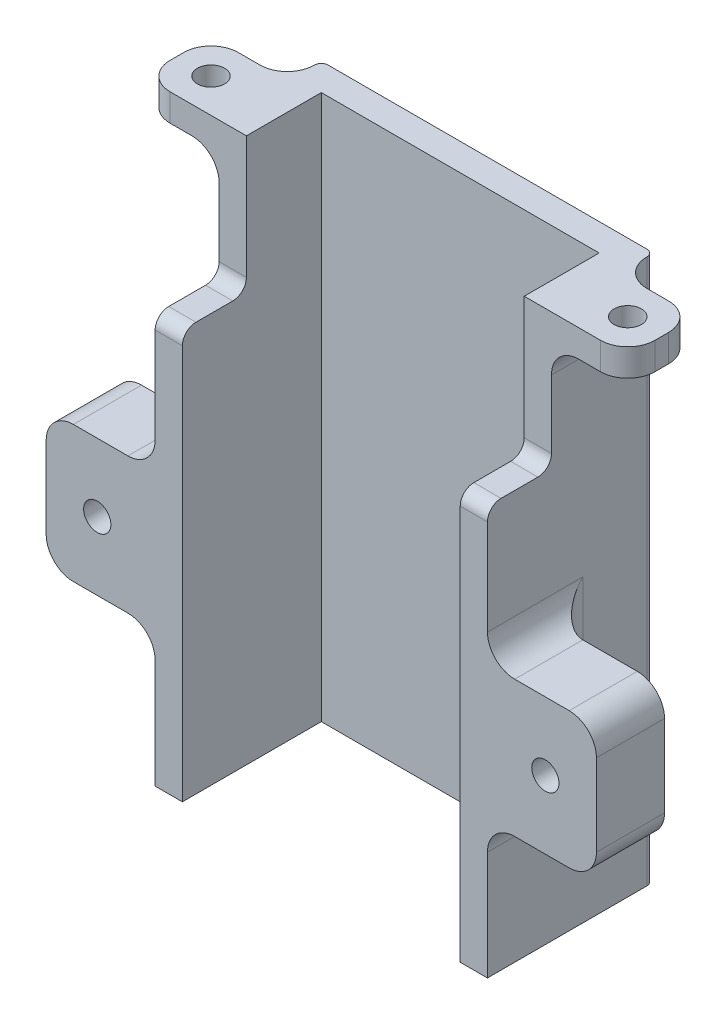
SolidWorks part; units mm, degrees
ref_plane "Front Plane" through (0, 0, 0) normal (0, 0, 1) x (1, 0, 0)
ref_plane "Top Plane" through (0, 0, 0) normal (0, 1, 0) x (1, 0, 0)
ref_plane "Right Plane" through (0, 0, 0) normal (1, 0, 0) x (0, 0, -1)
sketch "Sketch1" plane through (0, 0, 0) normal (0, 1, 0) x (1, 0, 0)
  line L1 (-25.908, 12.954) -> (25.908, 12.954)
  line L2 (-25.908, 12.954) -> (-25.908, -12.954)
  line L3 (-25.908, -12.954) -> (25.908, -12.954)
  line L4 (25.908, 12.954) -> (25.908, -12.954)
  line L5 (-25.908, 12.954) -> (25.908, -12.954) construction
  line L6 (-25.908, -12.954) -> (25.908, 12.954) construction
  line L7 (-30.988, -12.954) -> (30.988, -12.954)
  line L8 (-30.988, -12.954) -> (-30.988, 18.034)
  line L9 (-30.988, 18.034) -> (30.988, 18.034)
  line L10 (30.988, -12.954) -> (30.988, 18.034)
  point P0 (0, 0)
  dimension "D1" = 51.816
  dimension "D2" = 25.908
  dimension "D3" = 5.08
  dimension "D4" = 5.08
  dimension "D5" = 5.08
extrude "Boss-Extrude1" add sketch "Sketch1" along normal blind 101.6 contours L7 L10 L9 L8 L2 L1 L4 region at (-26.6009, 0, 0)
sketch "Sketch2" plane through (0, 0, 12.954) normal (0, 0, 1) x (1, 0, 0)
  line L0 (25.908, 101.6) -> (25.908, 0) construction
  line L1 (25.908, 25.4) -> (51.308, 25.4)
  line L2 (25.908, 25.4) -> (25.908, 50.8)
  line L3 (25.908, 50.8) -> (51.308, 50.8)
  line L4 (51.308, 25.4) -> (51.308, 50.8)
  line L5 (25.908, 101.6) -> (30.988, 101.6) construction
  line L6 (0, 0) -> (0, 80.1412) construction
  line L7 (-51.308, 25.4) -> (-51.308, 50.8)
  line L8 (-25.908, 50.8) -> (-51.308, 50.8)
  line L9 (-25.908, 25.4) -> (-25.908, 50.8)
  line L10 (-25.908, 25.4) -> (-51.308, 25.4)
  dimension "D1" = 25.4
  dimension "D2" = 25.4
  dimension "D3" = 50.8
extrude "Boss-Extrude2" add sketch "Sketch2" against normal blind 12.7
sketch "Sketch3" plane through (0, 0, 0.254) normal (0, 0, -1) x (-1, 0, 0)
  line L0 (-51.308, 50.8) -> (-30.988, 50.8) construction
  line L1 (-51.308, 25.4) -> (-51.308, 50.8) construction
  line L2 (0, 73.8565) -> (0, 0) construction
  circle A0 centre (-41.783, 38.1) radius 2.54
  circle A1 centre (41.783, 38.1) radius 2.54
  dimension "D1" = 5.08
  dimension "D2" = 12.7
  dimension "D3" = 9.525
extrude "Cut-Extrude1" cut sketch "Sketch3" against normal through all
sketch "Sketch4" plane through (0, 0, 0.254) normal (0, 0, -1) x (-1, 0, 0)
  circle A0 centre (-41.783, 38.1) radius 6.35
  circle A1 centre (41.783, 38.1) radius 6.35
  dimension "D1" = 12.7
  dimension "D2" = 12.7
extrude "Cut-Extrude2" cut sketch "Sketch4" against normal blind 5.08
fillet "Fillet1" radius 5.08 10 edges at (-51.308, 25.4, 6.604) (-51.308, 50.8, 6.604) (-30.988, 50.8, 6.604) (-30.988, 25.4, 6.604) (-30.988, 38.1, 0.254) (51.308, 50.8, 6.604) (51.308, 25.4, 6.604) (30.988, 25.4, 6.604) (30.988, 50.8, 6.604) (30.988, 38.1, 0.254)
sketch "Sketch5" plane through (0, 101.6, 0) normal (0, 1, 0) x (1, 0, 0)
  line L1 (30.988, -12.954) -> (-45.212, -12.954)
  line L2 (30.988, -12.954) -> (30.988, 37.846)
  line L3 (30.988, 37.846) -> (-45.212, 37.846)
  line L4 (-45.212, -12.954) -> (-45.212, 37.846)
  line L5 (-30.988, 18.034) -> (-45.212, 18.034)
  line L6 (-30.988, 18.034) -> (-30.988, -1.016)
  line L7 (-30.988, -1.016) -> (-45.212, -1.016)
  line L8 (-45.212, 18.034) -> (-45.212, -1.016)
  line L13 (0, 0) -> (0, 56.8559) construction
  line L15 (30.988, 18.034) -> (30.988, -1.016)
  line L18 (45.212, 18.034) -> (45.212, -1.016)
  line L19 (30.988, -1.016) -> (45.212, -1.016)
  line L20 (30.988, 18.034) -> (30.988, -1.016)
  line L21 (30.988, 18.034) -> (45.212, 18.034)
  line L22 (45.212, -12.954) -> (45.212, 37.846)
  line L23 (-45.212, 11.684) -> (45.212, 11.684)
  circle A1 centre (-38.862, 5.334) radius 2.54
  circle A2 centre (38.862, 5.334) radius 2.54
  line M9 (-30.988, 18.034) -> (-30.988, -12.954)
  dimension "D11" = 5.08
  dimension "D1" = 76.2
  dimension "D2" = 19.05
  dimension "D3" = 50.8
  dimension "D4" = 6.35
  dimension "D9" = 6.35
  dimension "D10" = 12.7
extrude "Boss-Extrude3" add sketch "Sketch5" against normal blind 5.08 contours L7 L5 L4 A1 M9 | L21 L2 L19 L18 A2 region at (31.1787, 101.6, -5.334) region at (-38.1, 101.6, 0.8253)
fillet "Fillet2" radius 5.08 4 edges at (-30.988, 96.52, -5.334) (30.988, 96.52, -5.334) (30.988, 99.06, -11.684) (-30.988, 99.06, -11.684)
fillet "Fillet3" radius 5.08 4 edges at (-45.212, 99.06, 1.016) (45.212, 99.06, 1.016) (-45.212, 99.06, -11.684) (45.212, 99.06, -11.684)
sketch "Sketch6" plane through (-30.988, 0, 0) normal (-1, 0, 0) x (0, 0, 1)
  line L0 (12.954, 101.6) -> (12.954, 55.88) construction
  line L1 (1.016, 101.6) -> (12.954, 101.6)
  line L2 (1.016, 101.6) -> (1.016, 76.2)
  line L3 (1.016, 76.2) -> (12.954, 76.2)
  line L4 (12.954, 101.6) -> (12.954, 76.2)
  dimension "D1" = 25.4
extrude "Cut-Extrude3" cut sketch "Sketch6" against normal through all
fillet "Fillet4" radius 2.54 4 edges at (-28.448, 76.2, 1.016) (-28.448, 76.2, 12.954) (28.448, 76.2, 12.954) (28.448, 76.2, 1.016)
fillet "Fillet5" radius 1.27 2 edges at (30.988, 50.8, -18.034) (-30.988, 50.8, -18.034)
